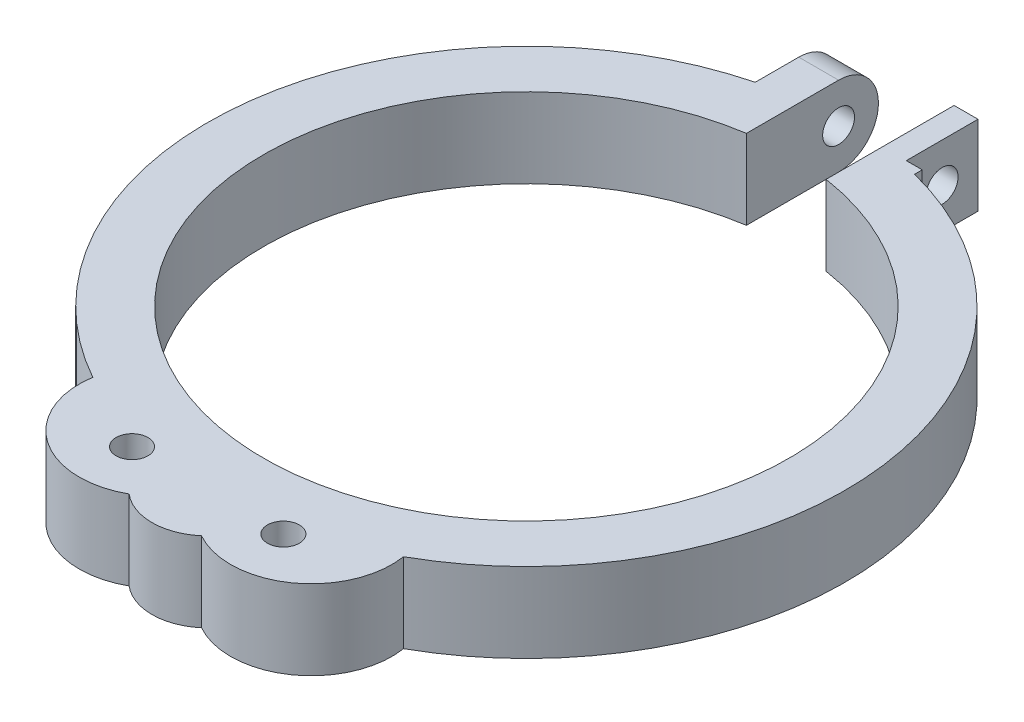
SolidWorks part; units mm, degrees
ref_plane "Alzado" through (0, 0, 0) normal (0, 0, 1) x (1, 0, 0)
ref_plane "Planta" through (0, 0, 0) normal (0, 1, 0) x (1, 0, 0)
ref_plane "Vista lateral" through (0, 0, 0) normal (1, 0, 0) x (0, 0, -1)
sketch "Croquis1" plane through (0, 0, 0) normal (0, 1, 0) x (1, 0, 0)
  line L0 (0, 0) -> (10, 0)
  line L1 (0, 0) -> (-10, 0)
  line L2 (10, 0) -> (10, 31.4484)
  line L3 (-10, 0) -> (-10, 31.4484)
  line L4 (10, 31.4484) -> (10, 38.7298)
  line L5 (-10, 31.4484) -> (-10, 38.7298)
  line L6 (5, 0) -> (5, 32.619)
  line L7 (5, 32.619) -> (5, 39.6863)
  line L8 (-5, 0) -> (-5, 32.619)
  line L9 (-5, 32.619) -> (-5, 39.6863)
  line L10 (5, 32.619) -> (10, 32.619)
  line L11 (-5, 39.6863) -> (-10, 39.6863)
  line L12 (-10, 39.6863) -> (-10, 38.7298)
  line L13 (5, 39.6863) -> (10, 39.6863)
  line L14 (10, 39.6863) -> (10, 38.7298)
  circle A0 centre (0, 0) radius 33
  circle A1 centre (0, 0) radius 40
extrude "Saliente-Extruir1" add sketch "Croquis1" along normal blind 10 contours L5 A1 L4 A0 | L9 A1 L5 A0 | L4 A1 L7 L10 | A1 L14 L13 | A1 L11 L12 | A0 L4 L10 region at (7.4401, 0, -35.9468) region at (8.4426, 0, -32.2495) region at (-7.5124, 0, -35.68) region at (11.1224, 0, -32.0337) region at (8.4409, 0, -39.384) region at (-8.4409, 0, -39.384)
sketch "Croquis2" plane through (0, 10, 0) normal (0, 1, 0) x (1, 0, 0)
  circle A2 centre (0, -40) radius 7
  arc A3 (-10, 38.7298) -> (10, 38.7298) centre (0, 0) ccw construction
  circle A4 centre (9.5, -36.5) radius 10.1242
  circle A5 centre (-9.5, -36.5) radius 10.1242
  arc M5 (-10, 38.7298) -> (10, 38.7298) centre (0, 0) ccw
extrude "Saliente-Extruir2" add sketch "Croquis2" against normal blind 10 contours A5 A2 M5 | A5 A2 M5 | A4 A5 A2 | A4 A2 M5 | A2 A4 M5 region at (3.9377, 10, 41.8856) region at (12.636, 10, 41.5711) region at (0, 10, 44.5871) region at (-3.9377, 10, 41.8856) region at (-12.636, 10, 41.5711)
sketch "Croquis3" plane through (-10, 0, 0) normal (-1, 0, 0) x (0, 0, 1)
  line L0 (-39.6863, 5) -> (-44.1863, 5)
  line L1 (-39.6863, 10) -> (-42.6863, 10)
  line L2 (-39.6863, 10) -> (-39.6863, 0)
  line L3 (-39.6863, 0) -> (-42.6863, 0)
  line L5 (-44.1863, 5) -> (-44.1863, 10)
  line L6 (-44.1863, 10) -> (-42.6863, 10)
  line L7 (-44.1863, 5) -> (-44.1863, 0)
  line L8 (-44.1863, 0) -> (-42.6863, 0)
  circle A0 centre (-44.1863, 5) radius 2
  circle A1 centre (-44.1863, 5) radius 5
  line M4 (-39.6863, 10) -> (-39.6863, 0)
extrude "Saliente-Extruir3" add sketch "Croquis3" against normal blind 5 contours A0 L1 M4 | A0 L3 M4 | L2 A1 L5 A0 L0 | L7 A1 L0 A0 M4 | L5 A1 L7 A0 region at (-10, 2.5636, -41.9305) region at (-10, 7.4364, -41.9305) region at (-10, 9.2198, -40.7384) region at (-10, 0.7802, -40.7384) region at (-10, 5, -46.5509)
sketch "Croquis5" plane through (5, 0, 0) normal (-1, 0, 0) x (0, 0, 1)
  line L0 (-39.6863, 10) -> (-48.6863, 10)
  line L1 (-48.6863, 10) -> (-48.6863, 0)
  line L2 (-48.6863, 0) -> (-39.6863, 0)
  line L3 (-39.6863, 0) -> (-39.6863, 10)
  circle A0 centre (-44.1863, 5) radius 2
extrude "Saliente-Extruir4" add sketch "Croquis5" against normal blind 3
ref_plane "Plano1" through (8, 0, -48.6863) normal (0, -1, 0) x (-1, 0, 0)
sketch "Croquis8" plane through (0, 10, 0) normal (0, 1, 0) x (1, 0, 0)
  circle A0 centre (9.5, -40) radius 2
  circle A1 centre (-9.5, -40) radius 2
extrude "Cortar-Extruir1" cut sketch "Croquis8" against normal blind 10
